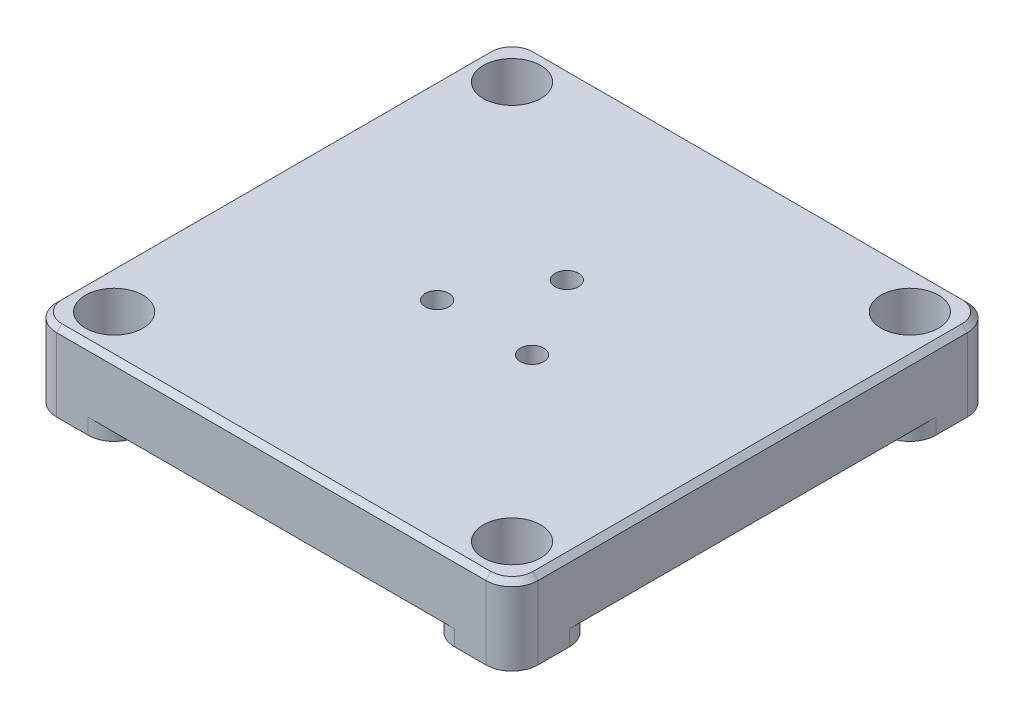
SolidWorks part; units mm, degrees
ref_plane "Спереди" through (0, 0, 0) normal (0, 0, 1) x (1, 0, 0)
ref_plane "Сверху" through (0, 0, 0) normal (0, 1, 0) x (1, 0, 0)
ref_plane "Справа" through (0, 0, 0) normal (1, 0, 0) x (0, 0, -1)
sketch "Эскиз1" plane through (0, 0, 0) normal (0, 1, 0) x (1, 0, 0)
  line L1 (-46.1, 46.1) -> (46.1, 46.1)
  line L2 (-46.1, 46.1) -> (-46.1, -46.1)
  line L3 (-46.1, -46.1) -> (46.1, -46.1)
  line L4 (46.1, 46.1) -> (46.1, -46.1)
  line L5 (-46.1, 46.1) -> (46.1, -46.1) construction
  line L6 (-46.1, -46.1) -> (46.1, 46.1) construction
  line L7 (38.1, 38.1) -> (-38.1, 38.1) construction
  line L8 (38.1, 38.1) -> (38.1, -38.1) construction
  line L9 (38.1, -38.1) -> (-38.1, -38.1) construction
  line L10 (-38.1, 38.1) -> (-38.1, -38.1) construction
  line L11 (38.1, 38.1) -> (-38.1, -38.1) construction
  line L12 (38.1, -38.1) -> (-38.1, 38.1) construction
  circle A0 centre (0, 0) radius 10.5 construction
  circle A1 centre (0, 10.5) radius 2.25
  circle A2 centre (-38.1, 38.1) radius 3.5
  circle A3 centre (38.1, 38.1) radius 3.5
  circle A4 centre (38.1, -38.1) radius 3.5
  circle A5 centre (-38.1, -38.1) radius 3.5
  circle A6 centre (9.0933, -5.25) radius 2.25
  circle A7 centre (-9.0933, -5.25) radius 2.25
  point P0 (0, 0)
  point P6 (0, 0)
  dimension "D4" = 21
  dimension "D5" = 4.5
  dimension "D6" = 7
  dimension "D7" = 7
  dimension "D8" = 7
  dimension "D9" = 7
  dimension "D1" = 92.2
  dimension "D2" = 92.2
  dimension "D3" = 76.2
  dimension "D10" = 3
extrude "Бобышка-Вытянуть1" add sketch "Эскиз1" along normal blind 12
sketch "Эскиз2" plane through (0, 0, 0) normal (0, -1, 0) x (1, 0, 0)
  circle A0 centre (-9.0933, 5.25) radius 3.6
  circle A1 centre (9.0933, 5.25) radius 3.6
  circle A2 centre (0, -10.5) radius 3.6
  dimension "D1" = 7.2
  dimension "D2" = 7.2
  dimension "D3" = 7.2
extrude "Вырез-Вытянуть1" cut sketch "Эскиз2" against normal offset from surface (2 mm away) 10 up to face at (9.0933, 12, 7.5)
sketch "Эскиз3" plane through (0, 0, 0) normal (0, -1, 0) x (1, 0, 0)
  line L0 (30.1, 30.1) -> (46.1, 30.1)
  line L1 (-30.1, 30.1) -> (-46.1, 30.1)
  line L2 (-30.1, 30.1) -> (-30.1, 46.1)
  line L3 (-30.1, 46.1) -> (-46.1, 46.1)
  line L4 (-46.1, 30.1) -> (-46.1, 46.1)
  line L5 (-30.1, 30.1) -> (-46.1, 46.1) construction
  line L6 (-30.1, 46.1) -> (-46.1, 30.1) construction
  line L7 (30.1, 30.1) -> (30.1, 46.1)
  line L8 (30.1, 46.1) -> (46.1, 46.1)
  line L9 (46.1, 30.1) -> (46.1, 46.1)
  line L10 (30.1, -30.1) -> (30.1, -46.1)
  line L11 (30.1, -30.1) -> (46.1, -30.1)
  line L12 (46.1, -30.1) -> (46.1, -46.1)
  line L13 (30.1, -46.1) -> (46.1, -46.1)
  line L14 (-30.1, -30.1) -> (-46.1, -30.1)
  line L15 (-30.1, -30.1) -> (-30.1, -46.1)
  line L16 (-30.1, -46.1) -> (-46.1, -46.1)
  line L17 (-46.1, -30.1) -> (-46.1, -46.1)
  line L18 (46.1, 46.1) -> (46.1, -46.1) construction
  line L19 (-46.1, 46.1) -> (46.1, 46.1) construction
  circle A0 centre (-38.1, 38.1) radius 3.5
  circle A1 centre (38.1, 38.1) radius 3.5
  circle A2 centre (38.1, -38.1) radius 3.5
  circle A3 centre (-38.1, -38.1) radius 3.5
  circle A4 centre (38.1, 38.1) radius 3.5 construction
  point P0 (-38.1, 38.1)
  dimension "D1" = 4
  dimension "D2" = 4
extrude "Бобышка-Вытянуть2" add sketch "Эскиз3" along normal blind 3
sketch "Эскиз4" plane through (0, 12, 0) normal (0, 1, 0) x (1, 0, 0)
  circle A0 centre (38.1, 38.1) radius 5.5
  circle A1 centre (38.1, -38.1) radius 5.5
  circle A2 centre (-38.1, -38.1) radius 5.5
  circle A3 centre (-38.1, 38.1) radius 5.5
  circle A4 centre (-38.1, 38.1) radius 3.5 construction
  dimension "D1" = 11
  dimension "D2" = 4
extrude "Вырез-Вытянуть2" cut sketch "Эскиз4" against normal offset from surface (10.8 mm away) 4.2 up to face at (38.1, -3, -38.1)
fillet "Скругление1" radius 5 16 edges at (-30.1, -1.5, 46.1) (-46.1, -1.5, 30.1) (-46.1, -1.5, -30.1) (-30.1, -1.5, -46.1) (30.1, -1.5, -46.1) (46.1, -1.5, -30.1) (46.1, -1.5, 30.1) (30.1, -1.5, 46.1) (-30.1, -1.5, 30.1) (30.1, -1.5, 30.1) (30.1, -1.5, -30.1) (-30.1, -1.5, -30.1) (-46.1, 4.5, -46.1) (46.1, 4.5, -46.1) (-46.1, 4.5, 46.1) (46.1, 4.5, 46.1)
chamfer "Фаска1" distance 1 angle 45 8 edges at (0, 12, -46.1) (-44.6355, 12, -44.6355) (44.6355, 12, -44.6355) (-46.1, 12, 0) (46.1, 12, 0) (-44.6355, 12, 44.6355) (44.6355, 12, 44.6355) (0, 12, 46.1)
equation "\"motor_diameter\"= 30"
equation "\"mm_diameter\"= IIF ( \"motor_diameter\" < 34 , 41 , \"motor_diameter\" + 8 )"
equation "\"upper_shafts_diameter\"= 5"
equation "\"upper_shats_length\"= 180"
equation "\"upper_bearing_d1\"= 10"
equation "\"upper_bearing_d2\"= 5"
equation "\"upper_bearing_h\"= 15"
equation "\"lower_shafts_diameter\"= 5"
equation "\"lower_shafts_length\"= 180"
equation "\"lower_bearing_d1\"= 10"
equation "\"lower_bearing_d2\"= 5"
equation "\"lower_bearing_h\"= 15"
equation "\"print_offset\"= 0.5"
equation "\"bh_screws_d\"= 2"
equation "\"bh_screws_h\"= 20"
equation "\"bh_screws_hh_d\"= 3.4"
equation "\"bh_screws_hh_h\"= 2"
equation "\"bh_nut_d\"= 3.8"
equation "\"bh_nut_h\"= 2"
equation "\"motor_screws_d\"= 3"
equation "\"motor_screws_h\"= 16"
equation "\"motor_screws_hh_d\"= 5.5"
equation "\"motor_screws_hh_h\"= 3"
equation "\"plate_hole_distance\"= 25.4"
equation "\"plate_screws_d\"= 6.5"
equation "\"shafts_diameter\"= IIF ( \"mm_diameter\" < 42 , 42 + 8 , \"mm_diameter\" + 8 )"
equation "\"central_hole_diameter\"= 8"
equation "\"bh_thikness\"= 4"
equation "\"ends_screws_d\"= 4"
equation "\"ends_screws_h\"= 16"
equation "\"ends_screws_hh_d\"= 6.7"
equation "\"ends_screws_hh_h\"= 4.1"
equation "\"ends_nut_d\"= 6.8"
equation "\"ends_nut_h\"= 3"
equation "\"D1@Эскиз1\"=\"D3@Эскиз1\"+16"
equation "\"D2@Эскиз1\"=\"D1@Эскиз1\""
equation "\"D3@Эскиз1\"=\"plate_hole_distance\"*3"
equation "\"D5@Эскиз1\"=\"ends_screws_d\"+\"print_offset\""
equation "\"D6@Эскиз1\"=\"plate_screws_d\"+\"print_offset\""
equation "\"D7@Эскиз1\"=\"D6@Эскиз1\""
equation "\"D8@Эскиз1\"=\"D6@Эскиз1\""
equation "\"D9@Эскиз1\"=\"D6@Эскиз1\""
equation "\"D1@Эскиз2\"=\"ends_screws_hh_d\"+\"print_offset\""
equation "\"D2@Эскиз2\"=\"D1@Эскиз2\""
equation "\"D3@Эскиз2\"=\"D1@Эскиз2\""
equation "\"D1@Вырез-Вытянуть1\"=\"ends_screws_h\"-6"
equation "\"system_radius\" = ( \"shafts_diameter\" + 12 + \"bh_thikness\" / 2 ) / 2"
equation "\"encoder_distance\"= \"system_radius\" + 4"
equation "\"tape_position\"= \"encoder_distance\" - 2 + 3.9 + 1.7 / 2"
equation "\"ft_sensor_d1\" = 9.8"
equation "\"ft_sensor_d2\"= 24.9"
equation "\"ft_sensor_h\"= 7"
equation "\"carbon_pipe_d\"= 14"
